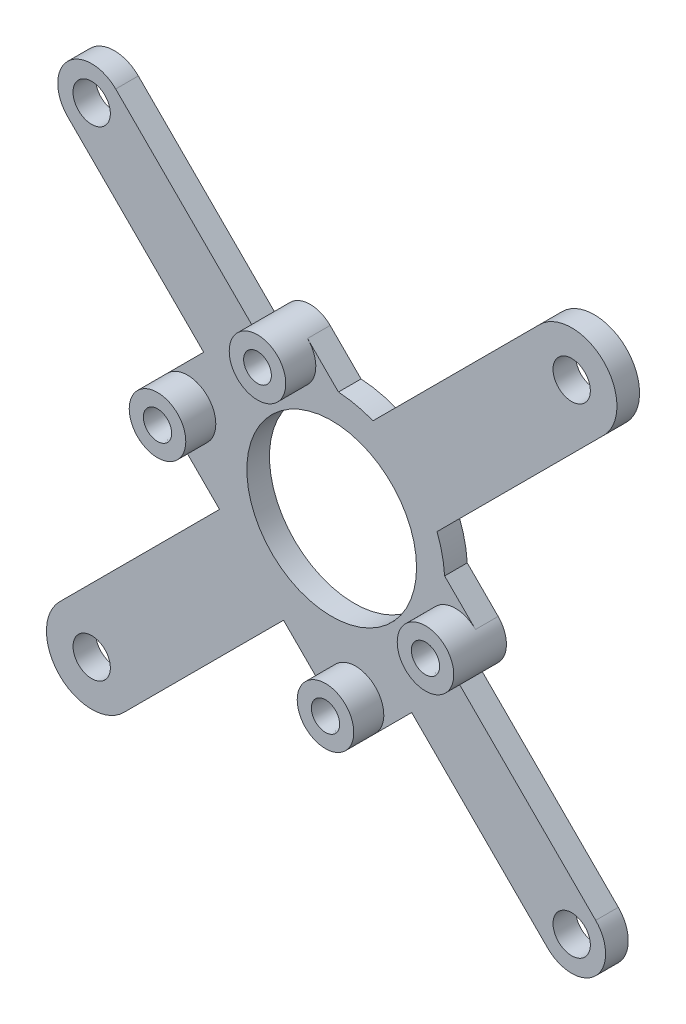
SolidWorks part; units mm, degrees
ref_plane "Front Plane" through (0, 0, 0) normal (0, 0, 1) x (1, 0, 0)
ref_plane "Top Plane" through (0, 0, 0) normal (0, 1, 0) x (1, 0, 0)
ref_plane "Right Plane" through (0, 0, 0) normal (1, 0, 0) x (0, 0, -1)
sketch "Sketch1" plane through (0, 0, 0) normal (0, 0, 1) x (1, 0, 0)
  line L0 (21.2132, 21.2132) -> (-2.1213, -2.1213) construction
  line L1 (24.0416, 18.3848) -> (9.3092, 3.6523)
  line L2 (18.3848, 24.0416) -> (3.6523, 9.3092)
  line L3 (-21.2132, 21.2132) -> (-7.0711, 7.0711) construction
  line L4 (-19.0919, 23.3345) -> (-4.624, 8.8667)
  line L5 (-23.3345, 19.0919) -> (-8.8667, 4.624)
  line L9 (-2.8284, 2.8284) -> (21.2132, -21.2132) construction
  line L11 (-9.3092, -3.6523) -> (-24.0416, -18.3848)
  line L12 (-7.0711, -7.0711) -> (-21.2132, -21.2132) construction
  line L13 (-3.6523, -9.3092) -> (-18.3848, -24.0416)
  line L14 (4.624, -8.8667) -> (19.0919, -23.3345)
  line L15 (8.8667, -4.624) -> (23.3345, -19.0919)
  circle A0 centre (21.2132, -21.2132) radius 1.65
  circle A1 centre (21.2132, 21.2132) radius 1.65
  circle A2 centre (-21.2132, 21.2132) radius 1.65
  circle A3 centre (-21.2132, -21.2132) radius 1.65
  arc A4 (24.0416, 18.3848) -> (18.3848, 24.0416) centre (21.2132, 21.2132) ccw
  arc A5 (-24.0416, -18.3848) -> (-18.3848, -24.0416) centre (-21.2132, -21.2132) ccw
  arc A6 (-19.0919, 23.3345) -> (-23.3345, 19.0919) centre (-21.2132, 21.2132) ccw
  arc A7 (19.0919, -23.3345) -> (23.3345, -19.0919) centre (21.2132, -21.2132) ccw
  arc A8 (3.6523, 9.3092) -> (-4.624, 8.8667) centre (0, 0) ccw
  arc A9 (8.8667, -4.624) -> (9.3092, 3.6523) centre (0, 0) ccw
  arc A10 (-8.8667, 4.624) -> (-9.3092, -3.6523) centre (0, 0) ccw
  arc A11 (-3.6523, -9.3092) -> (4.624, -8.8667) centre (0, 0) ccw
  point P12 (0, 0)
  point P17 (0, 0)
  dimension "D1" = 3.3
  dimension "D4" = 20
  dimension "D2" = 6
  dimension "D3" = 8
extrude "Boss-Extrude1" add sketch "Sketch1" along normal blind 2 contours L5 A7 L4 L1 A0 | L1 A4 L2 L4 A1 | L4 A6 L5 L2 A2 | L2 L5 L1 L4 | L2 A5 L1 L5 A3 region at (0, 0, 0)
sketch "Sketch2" plane through (0, 0, 2) normal (0, 0, 1) x (1, 0, 0)
  line L0 (-2.1355, 12.7138) -> (12.7138, -2.1355)
  line L1 (-14.5098, 0.3394) -> (0.3394, -14.5098)
  line L2 (-5.671, 12.7138) -> (-14.5098, 3.8749)
  line L3 (12.7138, -5.671) -> (3.8749, -14.5098)
  arc A0 (-13.5199, 2.885) -> (-11.9642, 1.3294) centre (-12.7421, 2.1072) ccw construction
  arc A1 (1.3294, -11.9642) -> (2.885, -13.5199) centre (2.1072, -12.7421) ccw construction
  arc A2 (11.7238, -4.681) -> (10.1682, -3.1254) centre (10.946, -3.9032) ccw construction
  arc A3 (-4.681, 11.7238) -> (-3.1254, 10.1682) centre (-3.9032, 10.946) ccw construction
  arc A4 (-13.5199, 2.885) -> (-11.9642, 1.3294) centre (-12.7421, 2.1072) ccw construction
  arc A5 (1.3294, -11.9642) -> (2.885, -13.5199) centre (2.1072, -12.7421) ccw construction
  arc A6 (11.7238, -4.681) -> (10.1682, -3.1254) centre (10.946, -3.9032) ccw construction
  arc A7 (-4.681, 11.7238) -> (-3.1254, 10.1682) centre (-3.9032, 10.946) ccw construction
  circle A8 centre (-3.9032, 10.946) radius 1.25
  circle A9 centre (10.946, -3.9032) radius 1.25
  circle A10 centre (2.1072, -12.7421) radius 1.25
  circle A11 centre (-12.7421, 2.1072) radius 1.25
  arc A12 (-2.1355, 12.7138) -> (-5.671, 12.7138) centre (-3.9032, 10.946) ccw
  arc A13 (-14.5098, 3.8749) -> (-14.5098, 0.3394) centre (-12.7421, 2.1072) ccw
  arc A14 (0.3394, -14.5098) -> (3.8749, -14.5098) centre (2.1072, -12.7421) ccw
  arc A15 (12.7138, -5.671) -> (12.7138, -2.1355) centre (10.946, -3.9032) ccw
  dimension "D1" = 2.5
  dimension "D2" = 5
extrude "Boss-Extrude2" add sketch "Sketch2" against normal up to surface (2 mm away) up to face at (22.8632, -21.2132, 0)
sketch "Sketch3" plane through (0, 0, 2) normal (0, 0, 1) x (1, 0, 0)
  circle A0 centre (0, 0) radius 7.5
  circle A1 centre (0, 0) radius 52.5 construction
  dimension "D1" = 15
extrude "Cut-Extrude1" cut sketch "Sketch3" against normal blind 2
sketch "Sketch4" plane through (0, 0, 2) normal (0, 0, 1) x (1, 0, 0)
  circle A0 centre (-3.9032, 10.946) radius 2.5
  circle A1 centre (-12.7421, 2.1072) radius 2.5
  circle A2 centre (10.946, -3.9032) radius 2.5
  circle A3 centre (2.1072, -12.7421) radius 2.5
  circle A4 centre (-12.7421, 2.1072) radius 1.25 construction
  circle A5 centre (-3.9032, 10.946) radius 1.25 construction
  circle A6 centre (2.1072, -12.7421) radius 1.25 construction
  circle A7 centre (10.946, -3.9032) radius 1.25 construction
  circle A8 centre (-12.7421, 2.1072) radius 1.25
  circle A9 centre (-3.9032, 10.946) radius 1.25
  circle A10 centre (2.1072, -12.7421) radius 1.25
  circle A11 centre (10.946, -3.9032) radius 1.25
extrude "Boss-Extrude3" add sketch "Sketch4" along normal up to surface (2.6541 mm away)
sketch "Sketch5" plane through (0, 0, 4.6541) normal (0, 0, 1) x (1, 0, 0)
  circle A0 centre (-3.9032, 10.946) radius 1.075
  circle A1 centre (-12.7421, 2.1072) radius 1.1
  circle A2 centre (2.1072, -12.7421) radius 1.1
  circle A3 centre (10.946, -3.9032) radius 1.1
  circle A4 centre (10.946, -3.9032) radius 1.7978
  circle A5 centre (2.1072, -12.7421) radius 2.0125
  circle A6 centre (-12.7421, 2.1072) radius 1.7291
  circle A7 centre (-3.9032, 10.946) radius 1.8132
  dimension "D1" = 2.15
extrude "Boss-Extrude4" add sketch "Sketch5" against normal up to surface (4.6541 mm away) up to face at (7.5, 0, 0)
chamfer "Chamfer1" distance 0.15 angle 85 4 edges at (-11.6421, 2.1072, 4.6541) (-2.8282, 10.946, 4.6541) (12.046, -3.9032, 4.6541) (3.2072, -12.7421, 4.6541) first distance on face at (-15.2421, 2.1072, 4.6541) first distance on face at (-6.4032, 10.946, 4.6541) first distance on face at (8.446, -3.9032, 4.6541) first distance on face at (-0.3928, -12.7421, 4.6541)
